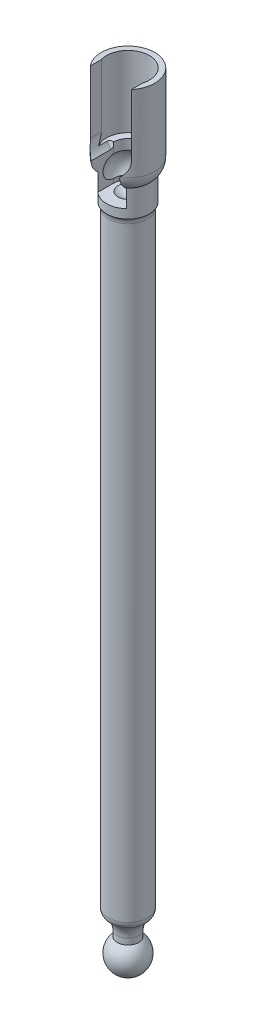
SolidWorks part; units mm, degrees
ref_plane "Front Plane" through (0, 0, 0) normal (0, 0, 1) x (1, 0, 0)
ref_plane "Top Plane" through (0, 0, 0) normal (0, 1, 0) x (1, 0, 0)
ref_plane "Right Plane" through (0, 0, 0) normal (1, 0, 0) x (0, 0, -1)
sketch "Esboço1" plane through (0, 0, 0) normal (0, 0, 1) x (1, 0, 0)
  line L0 (-10, 0) -> (10, 0) construction
  line L1 (-10, 0) -> (10, 0)
  arc A0 (10, 0) -> (-10, 0) centre (0, 0) ccw
  dimension "D1" = 20
revolve "Revolução1" add sketch "Esboço1" angle 360 about L0
sketch "Esboço2" plane through (0, 0, 0) normal (0, 1, 0) x (1, 0, 0)
  circle A0 centre (0, 0) radius 6
  dimension "D1" = 12
extrude "Ressalto-extrusão1" add sketch "Esboço2" along normal blind 20
sketch "Esboço3" plane through (0, 20, 0) normal (0, 1, 0) x (1, 0, 0)
  circle A0 centre (0, 0) radius 11
  dimension "D1" = 22
extrude "Ressalto-extrusão2" add sketch "Esboço3" along normal blind 350
fillet "Filete1" radius 10 1 edges at (0, 20, 6)
fillet "Filete2" radius 5 1 edges at (0, 20, 11)
sketch "Esboço4" plane through (0, 0, 0) normal (0, 0, 1) x (1, 0, 0)
  line L0 (0, 0) -> (0, 223.6213) construction
sketch "Esboço5" plane through (0, 370, 0) normal (0, 1, 0) x (1, 0, 0)
  line L0 (-8, 0) -> (6.7525, 0) construction
  line L4 (-8, -8.9443) -> (-8, 0)
  line L5 (8, -8.9443) -> (8, 0)
  line L7 (0, -8.7935) -> (0, 6.9875) construction
  arc A2 (-8, 8.9443) -> (-8, -8.9443) centre (0, 0) ccw
  arc A3 (8, -8.9443) -> (8, 8.9443) centre (0, 0) ccw
  arc A5 (8, 0) -> (-8, 0) centre (0, 0) ccw
  arc A6 (-8, 8.9443) -> (8, 8.9443) centre (0, 0) cw
  point P0 (-8, 0)
  dimension "D1" = 8
  dimension "D2" = 24
  dimension "D3" = 8
extrude "Ressalto-extrusão3" add sketch "Esboço5" along normal blind 20
sketch "Esboço7" plane through (0, 370, 0) normal (0, 1, 0) x (1, 0, 0)
  circle A0 centre (0, 0) radius 12
extrude "Ressalto-extrusão4" add sketch "Esboço7" against normal blind 5
fillet "Filete3" radius 5 1 edges at (0, 365, 11)
sketch "Esboço8" plane through (0, 0, 0) normal (0, 0, 1) x (1, 0, 0)
  line L0 (-12, 391.6405) -> (12, 365) construction
  line L1 (12, 365) -> (12, 390) construction
  line L2 (0, 368.3202) -> (0, 388.3202)
  line L3 (-12, 390) -> (-12, 365) construction
  arc A0 (0, 388.3202) -> (0, 368.3202) centre (0, 378.3202) ccw
  dimension "D1" = 20
revolve "Corte-Revolução1" cut sketch "Esboço8" angle 360 about L2
sketch "Esboço10" plane through (0, 390, 0) normal (0, 1, 0) x (1, 0, 0)
  line L0 (-8, -8.9443) -> (-8, -12.6886)
  line L1 (8, -8.9443) -> (8, -12.6886)
  arc A1 (8, -8.9443) -> (-8, -8.9443) centre (0, 0) ccw
  arc A2 (8, -12.6886) -> (-8, -12.6886) centre (0, 0) ccw
  dimension "D1" = 30
extrude "Ressalto-extrusão5" add sketch "Esboço10" along normal blind 40 and the other way blind 10
fillet "Filete4" radius 10 1 edges at (0, 380, -15)
sketch "Esboço11" plane through (0, 0, 0) normal (0, 0, 1) x (1, 0, 0)
  line L0 (-8, 430) -> (8, 387.1414) construction
  line L1 (15, 387.1414) -> (-15, 387.1414) construction
  line L2 (-11.5, 430) -> (11.5, 430)
  line L3 (-11.5, 430) -> (-11.5, 387.1414)
  line L4 (-11.5, 387.1414) -> (11.5, 387.1414)
  line L5 (11.5, 430) -> (11.5, 387.1414)
  line L6 (-11.5, 430) -> (11.5, 387.1414) construction
  line L7 (-11.5, 387.1414) -> (11.5, 430) construction
  point P4 (0, 408.5707)
  dimension "D1" = 23
extrude "Corte-extrusão3" cut sketch "Esboço11" along normal blind 40
fillet "Filete5" radius 10 2 edges at (11.5, 387.1414, 4.8153) (-11.5, 387.1414, 4.8153)
fillet "Filete6" radius 1.5 2 edges at (9.2848, 388.464, 0) (-9.2848, 388.464, 0)
sketch "Esboço9" plane through (0, 0, 0) normal (1, 0, 0) x (0, 0, -1)
  line L0 (-8.9443, 380) -> (-8.9443, 370) construction
  line L1 (-8.9443, 369.5279) -> (-8.9443, 380)
  line L2 (-8.9443, 380) -> (12, 380)
  line L3 (12, 380) -> (12, 369.5279)
  arc A0 (12, 369.5279) -> (-8.9443, 369.5279) centre (1.5279, 369.5279) ccw
